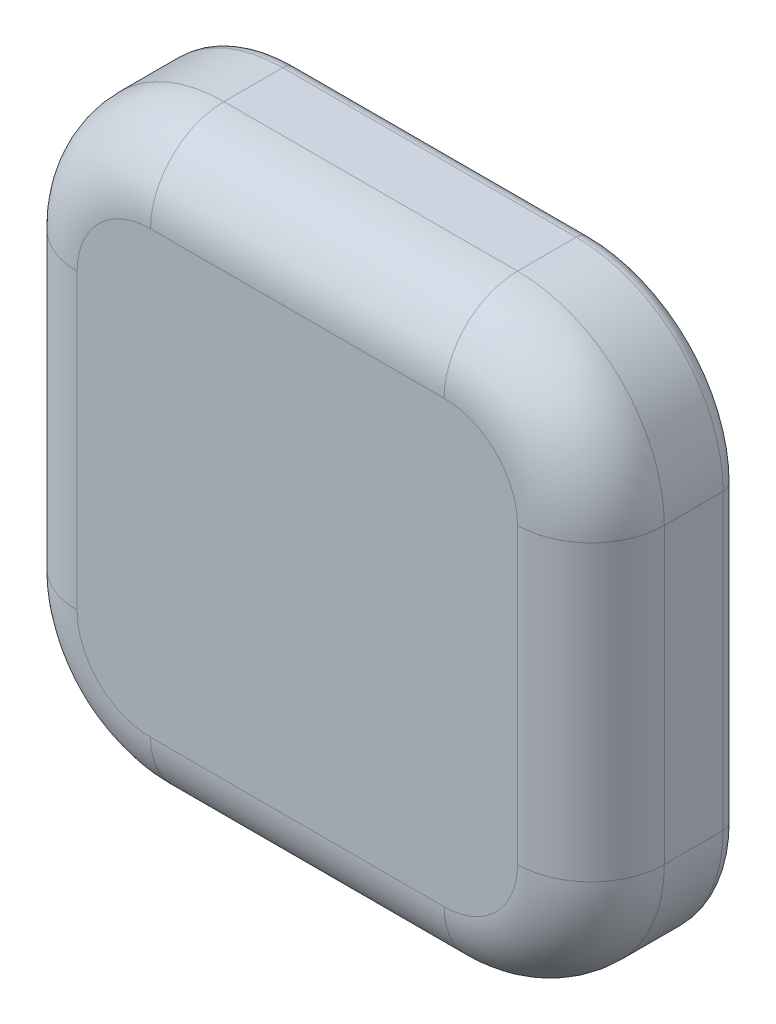
SolidWorks part; units mm, degrees
ref_plane "Plano frontal" through (0, 0, 0) normal (0, 0, 1) x (1, 0, 0)
ref_plane "Plano superior" through (0, 0, 0) normal (0, 1, 0) x (1, 0, 0)
ref_plane "Plano direito" through (0, 0, 0) normal (1, 0, 0) x (0, 0, -1)
sketch "Esboço1" plane through (0, 0, 0) normal (0, 0, 1) x (1, 0, 0)
  line L0 (4.25, 4.25) -> (-4.25, -4.25) construction
  line L1 (-4.25, 4.25) -> (4.25, 4.25)
  line L2 (-4.25, 4.25) -> (-4.25, -4.25)
  line L3 (-4.25, -4.25) -> (4.25, -4.25)
  line L4 (4.25, 4.25) -> (4.25, -4.25)
  line L5 (1.645, 1.645) -> (-1.645, -1.645) construction
  line L6 (-1.645, 1.645) -> (1.645, 1.645)
  line L7 (-1.645, 1.645) -> (-1.645, -1.645)
  line L8 (-1.645, -1.645) -> (1.645, -1.645)
  line L9 (1.645, 1.645) -> (1.645, -1.645)
  dimension "D1" = 8.5
  dimension "D2" = 8.5
  dimension "D3" = 3.29
  dimension "D4" = 3.29
extrude "Ressalto-extrusão1" add sketch "Esboço1" along normal blind 7.3
sketch "Esboço2" plane through (0, 0, 7.3) normal (0, 0, 1) x (1, 0, 0)
  line L0 (20, 20) -> (-20, -20) construction
  line L1 (-20, 20) -> (20, 20)
  line L2 (-20, 20) -> (-20, -20)
  line L3 (-20, -20) -> (20, -20)
  line L4 (20, 20) -> (20, -20)
  dimension "D1" = 40
  dimension "D2" = 40
extrude "Ressalto-extrusão2" add sketch "Esboço2" along normal blind 10
fillet "Filete1" radius 10 4 edges at (-4.25, 0, 7.3) (0, -4.25, 7.3) (4.25, 0, 7.3) (0, 4.25, 7.3)
fillet "Filete2" radius 10 4 edges at (20, 20, 12.3) (20, -20, 12.3) (-20, -20, 12.3) (-20, 20, 12.3)
fillet "Filete3" radius 5 8 edges at (17.0711, -17.0711, 17.3) (0, -20, 17.3) (-17.0711, -17.0711, 17.3) (-20, 0, 17.3) (-17.0711, 17.0711, 17.3) (0, 20, 17.3) (17.0711, 17.0711, 17.3) (20, 0, 17.3)
sketch "Esboço3" plane through (0, 0, 0) normal (0, 0, -1) x (-1, 0, 0)
  line L0 (-1.645, 1.645) -> (1.645, 1.645) construction
  line L1 (-0.25, 3.145) -> (0.25, 3.145)
  line L2 (-0.25, 3.145) -> (-0.25, 1.645)
  line L3 (-0.25, 1.645) -> (0.25, 1.645)
  line L4 (0.25, 3.145) -> (0.25, 1.645)
  line L5 (0, 0) -> (1.645, 0) construction
  line L6 (1.645, 1.645) -> (1.645, -1.645) construction
  line L7 (1.645, 0) -> (0, -1.645) construction
  line L8 (1.645, -1.645) -> (-1.645, -1.645) construction
  line L9 (0, -1.645) -> (0, 0) construction
  line L10 (0.25, -3.145) -> (0.25, -1.645)
  line L11 (-0.25, -1.645) -> (0.25, -1.645)
  line L12 (-0.25, -3.145) -> (-0.25, -1.645)
  line L13 (-0.25, -3.145) -> (0.25, -3.145)
  line L14 (-1.645, -1.645) -> (-1.645, 1.645) construction
  line L15 (1.645, 0.25) -> (1.645, -0.25)
  line L16 (-3.145, 0.25) -> (-1.645, 0.25)
  line L17 (-3.145, 0.25) -> (-3.145, -0.25)
  line L18 (-3.145, -0.25) -> (-1.645, -0.25)
  line L19 (-1.645, 0.25) -> (-1.645, -0.25)
  line L20 (3.145, -0.25) -> (1.645, -0.25)
  line L21 (3.145, 0.25) -> (3.145, -0.25)
  line L22 (3.145, 0.25) -> (1.645, 0.25)
  dimension "D1" = 0.25
  dimension "D2" = 0.25
  dimension "D3" = 1.5
  dimension "D4" = 0.5
  dimension "D5" = 1.5
  dimension "D6" = 0.25
extrude "Corte-extrusão1" cut sketch "Esboço3" against normal blind 5
fillet "Filete4" radius 1 8 edges at (-17.0711, 17.0711, 7.3) (-20, 0, 7.3) (-17.0711, -17.0711, 7.3) (0, -20, 7.3) (17.0711, -17.0711, 7.3) (20, 0, 7.3) (17.0711, 17.0711, 7.3) (0, 20, 7.3)
